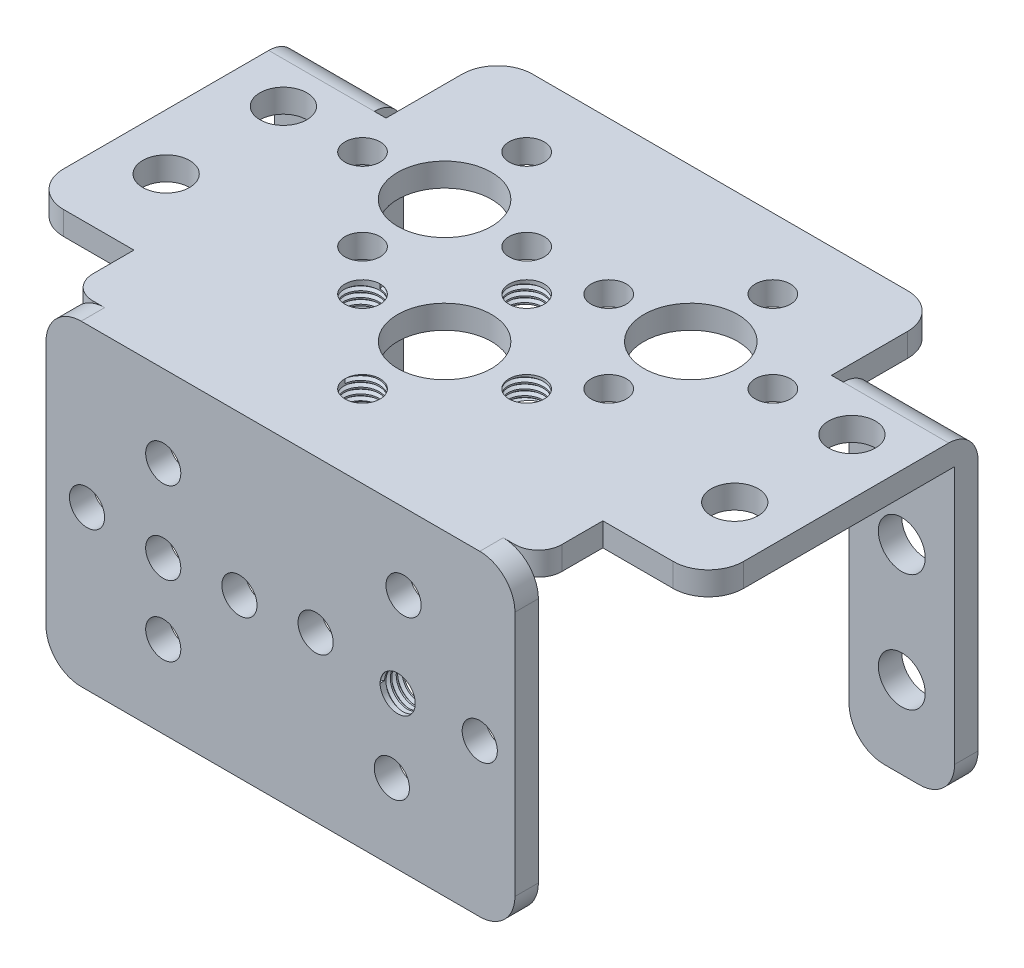
SolidWorks part; units mm, degrees
ref_plane "Front Plane" through (0, 0, 0) normal (0, 0, 1) x (1, 0, 0)
ref_plane "Top Plane" through (0, 0, 0) normal (0, 1, 0) x (1, 0, 0)
ref_plane "Right Plane" through (0, 0, 0) normal (1, 0, 0) x (0, 0, -1)
sketch "Sketch1" plane through (0, 0, 0) normal (0, 0, 1) x (1, 0, 0)
  line L0 (-10, 9.9105) -> (-10, -8.5447) construction
  line L1 (-20, -13.5) -> (20, -13.5)
  line L2 (-20, -13.5) -> (-20, 13.5)
  line L3 (-20, 13.5) -> (20, 13.5)
  line L4 (20, -13.5) -> (20, 13.5)
  line L5 (-20, -13.5) -> (20, 13.5) construction
  line L6 (-20, 13.5) -> (20, -13.5) construction
  line L7 (24.4064, 0) -> (-24.1877, 0) construction
  line L8 (0, -20.625) -> (0, 20.625) construction
  circle A0 centre (-10, -0.5) radius 1.5
  circle A1 centre (-10, -0.5) radius 7 construction
  circle A2 centre (10, -0.5) radius 7 construction
  circle A3 centre (10, -0.5) radius 1.5
  circle A4 centre (-10, 6.5) radius 1.5
  circle A5 centre (-3.5, 0) radius 1.5
  circle A6 centre (-10, -6.5) radius 1.5
  circle A7 centre (-16.5, 0) radius 1.5
  circle A8 centre (17, -0.5) radius 1.5
  circle A9 centre (9.5, -7) radius 1.5
  circle A10 centre (3, 0.5) radius 1.5
  circle A11 centre (10.5, 7) radius 1.5
  point P0 (0, 0)
  point P29 (-10, 0)
  point P38 (10, 0)
  dimension "D4" = 3
  dimension "D6" = 14
  dimension "D7" = 3
  dimension "D9" = 3
  dimension "D1" = 40
  dimension "D2" = 27
  dimension "D3" = 13
  dimension "D5" = 20
  dimension "D8" = 4
  dimension "D10" = 4
extrude "Boss-Extrude1" add sketch "Sketch1" along normal blind 2
fillet "Fillet1" radius 3 4 edges at (-20, -13.5, 1) (20, -13.5, 1) (20, 13.5, 1) (-20, 13.5, 1)
sketch "Sketch3" plane through (0, 13.5, 0) normal (0, 1, 0) x (1, 0, 0)
  line L16 (-20, 0) -> (-20, 5.5)
  line L17 (-20, 5.5) -> (-26, 5.5)
  line L18 (-29, 8.5) -> (-29, 28.5)
  line L19 (-29, 28.5) -> (-20, 28.5)
  line L20 (-20, 28.5) -> (-20, 26)
  line L21 (-20, 26) -> (-19, 26)
  line L22 (-19, 26) -> (-19, 35.5)
  line L23 (-19, 35.5) -> (19, 35.5)
  line L24 (19, 35.5) -> (19, 26)
  line L25 (19, 26) -> (20, 26)
  line L26 (20, 26) -> (20, 28.5)
  line L27 (20, 28.5) -> (29, 28.5)
  line L29 (0, -6.0304) -> (0, 48.0244) construction
  line L30 (29, 28.5) -> (29, 8.5)
  line L31 (26, 5.5) -> (20, 5.5)
  line L32 (20, 5.5) -> (20, 0)
  line L34 (-20, 0) -> (20, 0)
  line L35 (-33.8872, 22.5) -> (52.0246, 22.5) construction
  line L36 (-10.5, 33.8034) -> (-10.5, 11.2526) construction
  line L37 (10.5, 31.6205) -> (10.5, 10.7526) construction
  line L38 (0, 12) -> (31.9812, 12) construction
  circle A0 centre (-24.25, 22.5) radius 2
  circle A1 centre (-24.25, 12.5) radius 2
  circle A2 centre (24.25, 12.5) radius 2
  circle A3 centre (24.25, 22.5) radius 2
  arc A4 (29, 8.5) -> (26, 5.5) centre (26, 8.5) cw
  arc A5 (-26, 5.5) -> (-29, 8.5) centre (-26, 8.5) cw
  circle A6 centre (-10.5, 22.5) radius 4
  circle A7 centre (10.5, 22.5) radius 4
  circle A8 centre (-10.5, 22.5) radius 7 construction
  circle A9 centre (10.5, 22.5) radius 7 construction
  circle A10 centre (-10.5, 29.5) radius 1.5
  circle A11 centre (-3.5, 22.5) radius 1.5
  circle A12 centre (-10.5, 15.5) radius 1.5
  circle A13 centre (-17.5, 22.5) radius 1.5
  circle A14 centre (10.5, 29.5) radius 1.5
  circle A15 centre (17.5, 22.5) radius 1.5
  circle A16 centre (10.5, 15.5) radius 1.5
  circle A17 centre (3.5, 22.5) radius 1.5
  circle A18 centre (0, 12) radius 4
  circle A19 centre (0, 12) radius 7 construction
  circle A20 centre (0, 19) radius 1.5
  circle A21 centre (7, 12) radius 1.5
  circle A22 centre (0, 5) radius 1.5
  circle A23 centre (-7, 12) radius 1.5
  point P30 (-19.5, 26)
  point P57 (-10.5, 22.5)
  point P66 (10.5, 22.5)
  point P78 (0, 12)
  dimension "D7" = 4
  dimension "D8" = 4
  dimension "D15" = 3
  dimension "D16" = 8
  dimension "D17" = 14
  dimension "D18" = 3
  dimension "D20" = 3
  dimension "D23" = 8
  dimension "D24" = 14
  dimension "D25" = 3
  dimension "D27" = 21
  dimension "D1" = 35.5
  dimension "D2" = 58
  dimension "D3" = 28.5
  dimension "D4" = 38
  dimension "D5" = 28.5
  dimension "D6" = 10
  dimension "D9" = 12.5
  dimension "D10" = 48.5
  dimension "D11" = 2.5
  dimension "D12" = 2.5
  dimension "D13" = 5.5
  dimension "D14" = 5.5
  dimension "D22" = 12
  dimension "D19" = 4
  dimension "D21" = 4
  dimension "D26" = 4
extrude "Boss-Extrude4" add sketch "Sketch3" against normal blind 2
fillet "Fillet2" radius 3 2 edges at (19, 12.5, -35.5) (-19, 12.5, -35.5)
fillet "Fillet4" radius 2 2 edges at (20, 12.5, 0) (-20, 12.5, 0)
sketch "Sketch10" plane through (0, 0, -28.5) normal (0, 0, -1) x (-1, 0, 0)
  line L0 (29, 11.5) -> (29, -9.5)
  line L5 (29, 13.5) -> (29, 11.5)
  line L6 (-29, 13.5) -> (-29, -10.5)
  line L11 (20, 13.5) -> (20, -9.5)
  line L12 (26, -12.5) -> (23, -12.5)
  line L13 (20, 13.5) -> (29, 13.5)
  line L14 (-20, 13.5) -> (-20, -10.5)
  line L15 (-20, -10.5) -> (-20, 10.5) construction
  line L16 (-23, -13.5) -> (-26, -13.5)
  line L17 (-20, 13.5) -> (-29, 13.5)
  line L19 (0, -21.1887) -> (0, 20.1866) construction
  arc A0 (-29, -10.5) -> (-26, -13.5) centre (-26, -10.5) ccw
  arc A1 (-20, -10.5) -> (-23, -13.5) centre (-23, -10.5) cw
  arc A2 (20, -9.5) -> (23, -12.5) centre (23, -9.5) ccw
  arc A3 (29, -9.5) -> (26, -12.5) centre (26, -9.5) cw
  circle A4 centre (24.5, -6.5) radius 2
  circle A5 centre (24.5, 3.5) radius 2
  circle A6 centre (-24.5, 3.5) radius 2
  circle A7 centre (-24.5, -6.5) radius 2
  point P20 (-20, -13.5)
  point P23 (20, -12.5)
  point P26 (29, -12.5)
  dimension "D4" = 3
  dimension "D5" = 4
  dimension "D6" = 4
  dimension "D1" = 9
  dimension "D2" = 26
  dimension "D3" = 27
  dimension "D7" = 49
  dimension "D8" = 10
  dimension "20" = 20
extrude "Boss-Extrude5" add sketch "Sketch10" against normal blind 2
fillet "Fillet5" radius 2.5 2 edges at (-24.5, 13.5, -28.5) (24.5, 13.5, -28.5)
thread "Thread1" pitch 0.5 start angle 0, offset 0, length 2, pitch 0.5, diameter 3
ref_plane "Plane1" through (-1.5, 13.5, -5) normal (0, 0, 1) x (-1, 0, 0)
sketch "Thread Profile1" plane through (-1.5, 13.5, -5) normal (0, 0, 1) x (-1, 0, 0)
  line L0 (0, 0) -> (0, 0.5) construction
  line L1 (0, 0) -> (0.2706, 0.1562)
  line L2 (0.2706, 0.1562) -> (0.2706, 0.2187)
  line L3 (0.2706, 0.2187) -> (0, 0.375)
  line L4 (0.2706, 0.1875) -> (0, 0.1875) construction
  line L11 (0, 0) -> (0, 0.375)
  point P2 (0, 0)
  dimension "Pitch" = 0.5
  dimension "Profile_Angle" = 60
  dimension "Profile_Land" = 0.0625
  dimension "Profile_Height" = 0.2706
pattern_circular "CirPattern1" count 4 every 90 about axis through (0, 11.5, -12) along (0, 1, 0) of "Thread1"
thread "Thread2" pitch 0.5 profile "Thread Profile2" start angle 0, offset 0, length 2, pitch 0.5, diameter 3
ref_plane "Plane2" through (8.5, -0.5, 2) normal (0, -1, 0) x (-1, 0, 0)
sketch "Thread Profile2" plane through (8.5, -0.5, 2) normal (0, -1, 0) x (-1, 0, 0)
  line L0 (0, 0) -> (0, 0.5) construction
  line L1 (0, 0) -> (0.2706, 0.1562)
  line L2 (0.2706, 0.1562) -> (0.2706, 0.2187)
  line L3 (0.2706, 0.2187) -> (0, 0.375)
  line L4 (0.2706, 0.1875) -> (0, 0.1875) construction
  line L11 (0, 0) -> (0, 0.375)
  point P2 (0, 0)
  dimension "Pitch" = 0.5
  dimension "Profile_Angle" = 60
  dimension "Profile_Land" = 0.0625
  dimension "Profile_Height" = 0.2706
